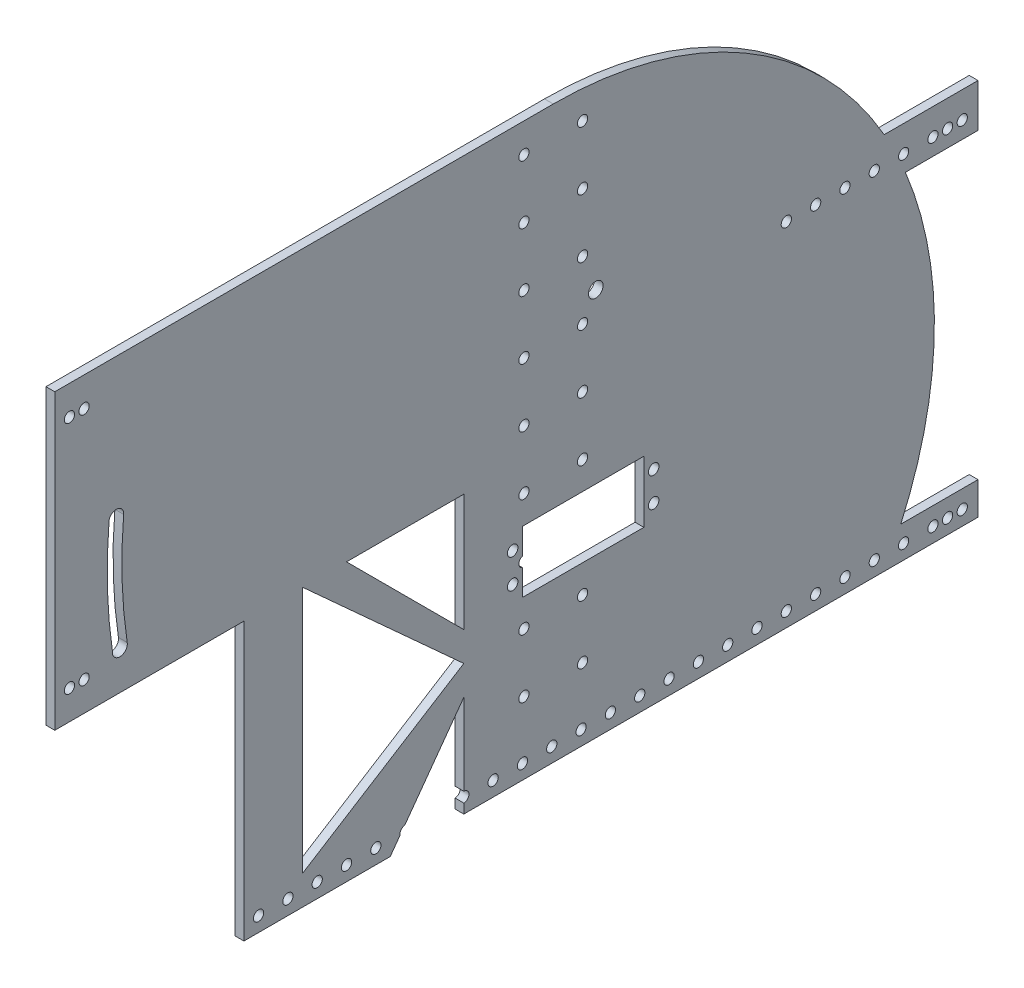
SolidWorks part; units mm, degrees
ref_plane "Front Plane" through (0, 0, 0) normal (0, 0, 1) x (1, 0, 0)
ref_plane "Top Plane" through (0, 0, 0) normal (0, 1, 0) x (1, 0, 0)
ref_plane "Right Plane" through (0, 0, 0) normal (1, 0, 0) x (0, 0, -1)
sketch "Sketch1" plane through (0, 0, 0) normal (1, 0, 0) x (0, 0, -1)
  line L0 (0, 130) -> (-170, 130)
  line L1 (-170, 130) -> (-170, 30)
  line L2 (-170, 30) -> (-126.4911, 30)
  arc A0 (-126.4911, 30) -> (0, 130) centre (0, 0) ccw
  circle A1 centre (0, 0) radius 5
  dimension "D1" = 260
  dimension "D2" = 10
  dimension "D3" = 100
  dimension "D4" = 170
extrude "Boss-Extrude1" add sketch "Sketch1" along normal blind 3
sketch "Sketch2" plane through (3, 0, 0) normal (1, 0, 0) x (0, 0, -1)
  line L0 (-10, 10) -> (-10, -10) construction
  line L1 (-10, -10) -> (30.4, -10) construction
  line L2 (30.4, -10) -> (30.4, 10) construction
  line L3 (30.4, 10) -> (-10, 10) construction
  line L4 (30.9, 10.5) -> (-10.5, 10.5)
  line L5 (-10.5, 10.5) -> (-10.5, -10.5)
  line L6 (-10.5, -10.5) -> (30.9, -10.5)
  line L7 (30.9, -10.5) -> (30.9, 10.5)
  circle A1 centre (0, 0) radius 5 construction
  circle A2 centre (-13.85, 5) radius 1.8
  circle A3 centre (-13.85, -5) radius 1.8
  circle A4 centre (34.25, 5) radius 1.8
  circle A5 centre (34.25, -5) radius 1.8
  point P11 (-10, 0)
  dimension "D1" = 10
  dimension "D2" = 10
  dimension "D4" = 3.6
  dimension "D7" = 3.85
  dimension "D8" = 5
  dimension "D10" = 5
  dimension "D12" = 3.85
  dimension "D13" = 10
  dimension "D3" = 40.4
  dimension "D5" = 20
  dimension "D9" = 10
  dimension "D11" = 3.85
  dimension "D6" = 0.5
extrude "ServoHole" cut sketch "Sketch2" against normal through all
sketch "Sketch3" plane through (3, 0, 0) normal (1, 0, 0) x (0, 0, -1)
  line L1 (123.9473, -130) -> (-198.7557, -130)
  line L2 (123.9473, -130) -> (123.9473, -64.5)
  line L3 (123.9473, -64.5) -> (-198.7557, -64.5)
  line L4 (-198.7557, -130) -> (-198.7557, -64.5)
  arc A0 (-126.4911, 30) -> (0, 130) centre (0, 0) ccw construction
  dimension "D1" = 130
  dimension "D2" = 64.5
extrude "Cut-Extrude2" cut sketch "Sketch3" against normal through all
sketch "Sketch4" plane through (3, 0, 0) normal (1, 0, 0) x (0, 0, -1)
  line L1 (-170, 30) -> (-105.5, 30)
  line L2 (-170, 30) -> (-170, -85)
  line L3 (-170, -85) -> (-105.5, -85)
  line L4 (-30.5, 30) -> (-30.5, -10)
  line L5 (-10.5, 10.5) -> (-10.5, -10.5) construction
  line L6 (-70.5, 30) -> (-30.5, -10)
  line L7 (-85.5, 30) -> (-30.5, -20)
  line L8 (-30.5, -20) -> (-85.5, -54.5)
  line L9 (-30.5, -30) -> (-70.5, -85)
  line L10 (-70.5, 30) -> (-30.5, 30)
  line L11 (-30.5, -30) -> (-30.5, -85)
  line L12 (-70.5, -85) -> (-30.5, -85)
  line L13 (-85.5, 30) -> (-85.5, -54.5)
  line L14 (-105.5, 30) -> (-105.5, -85)
  line L15 (112.8705, -64.5) -> (-112.8705, -64.5) construction
  dimension "D1" = 20
  dimension "D2" = 40
  dimension "D3" = 45
  dimension "D4" = 10
  dimension "D5" = 10
  dimension "D6" = 15
  dimension "D7" = 20
  dimension "D8" = 40
  dimension "D9" = 20
  dimension "D10" = 10
  dimension "D11" = 115
extrude "Cut-Extrude5" cut sketch "Sketch4" against normal through all
sketch "Sketch5" plane through (3, 0, 0) normal (1, 0, 0) x (0, 0, -1)
  line L0 (112.8705, -64.5) -> (-30.5, -64.5) construction
  line L1 (-30.5, -64.5) -> (-30.5, -30) construction
  circle A0 centre (-20.5, -59.5) radius 1.75
  dimension "D1" = 3.5
  dimension "D2" = 5
  dimension "D3" = 10
extrude "Cut-Extrude6" cut sketch "Sketch5" against normal blind 10
pattern_linear "LPattern1" count 14 spacing 10 along (0, 0, -1) of "Cut-Extrude6"
pattern_linear "LPattern2" count 14 spacing 10 along (0, 0, 1) of "Cut-Extrude6"
sketch "Sketch6" plane through (3, 0, 0) normal (1, 0, 0) x (0, 0, -1)
  circle A0 centre (109.5, 55.5) radius 1.75
  circle A1 centre (109.5, -59.5) radius 1.75 construction
  circle A2 centre (99.5, -59.5) radius 1.75 construction
  circle A3 centre (99.5, 55.5) radius 1.75
  circle A4 centre (89.5, 55.5) radius 1.75
  circle A5 centre (79.5, 55.5) radius 1.75
  dimension "D1" = 3.5
  dimension "D2" = 115
  dimension "D3" = 10
  dimension "D5" = 10
  dimension "D4" = 4
extrude "Cut-Extrude7" cut sketch "Sketch6" against normal blind 10
sketch "Sketch7" plane through (3, 0, 0) normal (1, 0, 0) x (0, 0, -1)
  line L0 (112.8705, -64.5) -> (144.8705, -64.5)
  line L1 (144.8705, -64.5) -> (144.8705, -53.383)
  line L2 (144.8705, -53.383) -> (118.5338, -53.383)
  line L3 (112.8705, 64.5) -> (144.8705, 64.5)
  line L4 (144.8705, 64.5) -> (144.8705, 49.7546)
  line L5 (144.8705, 49.7546) -> (120.102, 49.7546)
  arc A0 (112.8705, -64.5) -> (0, 130) centre (0, 0) ccw construction
  arc A1 (112.8705, -64.5) -> (118.5338, -53.383) centre (0, 0) ccw
  arc A2 (120.102, 49.7546) -> (112.8705, 64.5) centre (0, 0) ccw
  circle A3 centre (109.5, -59.5) radius 1.75 construction
  circle A4 centre (109.5, 55.5) radius 1.75 construction
  circle A5 centre (109.5, -59.5) radius 1.75 construction
  circle A6 centre (109.5, 55.5) radius 1.75 construction
  circle A7 centre (119.5, 55.5) radius 1.75
  circle A8 centre (129.5, 55.5) radius 1.75
  circle A9 centre (139.5, 55.5) radius 1.75
  circle A11 centre (119.5, -59.5) radius 1.75
  circle A12 centre (129.5, -59.5) radius 1.75
  circle A13 centre (139.5, -59.5) radius 1.75
  circle A15 centre (149.5, 55.5) radius 1.75 [skipped]
  circle A16 centre (149.5, -59.5) radius 1.75 [skipped]
  circle A17 centre (134.5, -59.5) radius 1.75
  circle A18 centre (134.5, 55.5) radius 1.75
  dimension "D4" = 10
  dimension "D6" = 5
  dimension "D8" = 10
  dimension "D10" = 5
  dimension "D3" = 32
  dimension "D7" = 32
  dimension "D1" = 5
  dimension "D2" = 5
  dimension "D5" = 2
  dimension "D9" = 2
extrude "Boss-Extrude2" add sketch "Sketch7" against normal blind 3
sketch "Sketch8" plane through (0, 0, 0) normal (-1, 0, 0) x (0, 0, 1)
  circle A0 centre (-14.5, 67.89) radius 2.5
  circle A1 centre (-79.5, 55.5) radius 1.75 construction
  arc A2 (146.5155, 82.0337) -> (145.2961, 43.5745) centre (-14.5, 67.89) cw
  arc A3 (151.5342, 82.0337) -> (150.3519, 43.5745) centre (-14.5, 67.89) cw
  arc A4 (145.2961, 43.5745) -> (150.3519, 43.5745) centre (147.824, 43.1898) ccw
  arc A5 (146.5155, 82.0337) -> (151.5342, 82.0337) centre (149.0248, 82.2541) cw
  dimension "D1" = 5
  dimension "D2" = 65
  dimension "D3" = 12.39
  dimension "D4" = 5
extrude "Cut-Extrude8" cut sketch "Sketch8" against normal blind 3
sketch "Sketch9" plane through (0, 0, 0) normal (-1, 0, 0) x (0, 0, 1)
  line L0 (0, 130) -> (170, 130) construction
  line L1 (170, 130) -> (170, 30) construction
  line L2 (170, 30) -> (105.5, 30) construction
  circle A0 centre (160, 40) radius 1.75
  circle A2 centre (160, 120) radius 1.75
  circle A4 centre (165, 40) radius 1.75
  circle A5 centre (165, 120) radius 1.75
  dimension "D1" = 3.5
  dimension "D2" = 10
  dimension "D3" = 10
  dimension "D4" = 10
  dimension "D5" = 10
  dimension "D6" = 2
extrude "Cut-Extrude9" cut sketch "Sketch9" against normal blind 10
sketch "Sketch10" plane through (0, 0, 0) normal (-1, 0, 0) x (0, 0, 1)
  line L0 (-144.8705, -64.5) -> (30.5, -64.5) construction
  line L4 (0, 130) -> (0, -64.5) construction
  line L5 (170, 130) -> (170, 30) construction
  line L6 (0, 130) -> (170, 130) construction
  circle A0 centre (10, 120) radius 1.75
  circle A2 centre (10, 100) radius 1.75
  circle A3 centre (10, 80) radius 1.75
  circle A4 centre (10, 60) radius 1.75
  circle A5 centre (10, 40) radius 1.75
  circle A6 centre (10, 20) radius 1.75
  circle A7 centre (10, 0) radius 1.75
  circle A8 centre (10, -20) radius 1.75
  circle A9 centre (10, -40) radius 1.75
  circle A10 centre (-10, 20) radius 1.75
  circle A11 centre (-10, -20) radius 1.75
  circle A12 centre (-10, -40) radius 1.75
  circle A13 centre (-10, 40) radius 1.75
  circle A14 centre (-10, 60) radius 1.75
  circle A15 centre (-10, 80) radius 1.75
  circle A16 centre (-10, 100) radius 1.75
  circle A17 centre (-10, 120) radius 1.75
  dimension "D2" = 10
  dimension "D3" = 10
  dimension "D4" = 3.5
  dimension "D6" = 20
  dimension "D1" = 170
  dimension "D5" = 9
extrude "Cut-Extrude10" cut sketch "Sketch10" against normal blind 10
sketch "Sketch11" plane through (0, 0, 0) normal (-1, 0, 0) x (0, 0, 1)
  line L0 (-144.8705, -64.5) -> (30.5, -64.5) construction
  line L1 (170, 130) -> (0, 130)
  line L2 (170, 130) -> (170, -64.5)
  line L3 (170, -64.5) -> (0, -64.5)
  line L4 (0, 130) -> (0, -64.5)
  dimension "D1" = 170
extrude "Cut-Extrude11" [suppressed] cut sketch "Sketch11" against normal blind 10
sketch "Sketch12" plane through (0, 0, 0) normal (-1, 0, 0) x (0, 0, 1)
  line L0 (0, 130) -> (170, 130) construction
  line L1 (-144.8705, -64.5) -> (0, -64.5)
  line L2 (-144.8705, -64.5) -> (-144.8705, 130)
  line L3 (-144.8705, 130) -> (0, 130)
  line L4 (0, -64.5) -> (0, 130)
  line L5 (170, 130) -> (170, 30) construction
  dimension "D1" = 170
extrude "Cut-Extrude12" [suppressed] cut sketch "Sketch12" against normal blind 10
